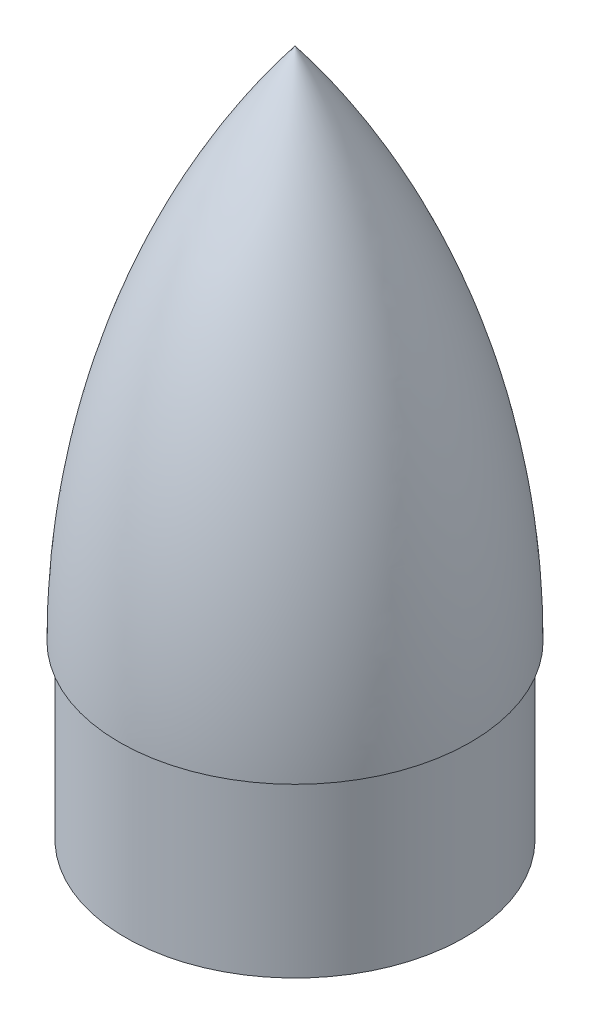
SolidWorks part; units mm, degrees
ref_plane "Front Plane" through (0, 0, 0) normal (0, 0, 1) x (1, 0, 0)
ref_plane "Top Plane" through (0, 0, 0) normal (0, 1, 0) x (1, 0, 0)
ref_plane "Right Plane" through (0, 0, 0) normal (1, 0, 0) x (0, 0, -1)
sketch "Sketch1" plane through (0, 0, 0) normal (0, 0, 1) x (1, 0, 0)
  line L0 (0, 0) -> (51.054, 0)
  line L1 (0, 0) -> (0, 150)
  line L2 (-194.8279, 0) -> (0, 0) construction
  line L3 (0, 0) -> (0, -163659.1195) construction
  arc A0 (51.054, 0) -> (0, 150) centre (-194.8279, 0) ccw
  dimension "D1" = 102.108
  dimension "D2" = 150
revolve "Revolve1" add sketch "Sketch1" angle 360 about L1
sketch "Sketch2" plane through (0, 0, 0) normal (0, -1, 0) x (1, 0, 0)
  circle A0 centre (0, 0) radius 49.403
  dimension "D1" = 98.806
extrude "Boss-Extrude1" add sketch "Sketch2" along normal blind 50
shell "Shell1" thickness 5 removed face at (0, -50, -49.403)
fillet "Fillet1" radius 10 1 edges at (0, 5, -46.0021)
sketch "Sketch3" plane through (0, 0, 0) normal (0, 0, 1) x (1, 0, 0)
  circle A0 centre (0, 70) radius 8
  dimension "D1" = 70
  dimension "D2" = 16
extrude "Boss-Extrude2" add sketch "Sketch3" along normal up to next and the other way up to next
fillet "Fillet2" radius 10 2 edges at (3.4776, 77.2046, -33.1646) (5.599, 75.7141, 33.379)
